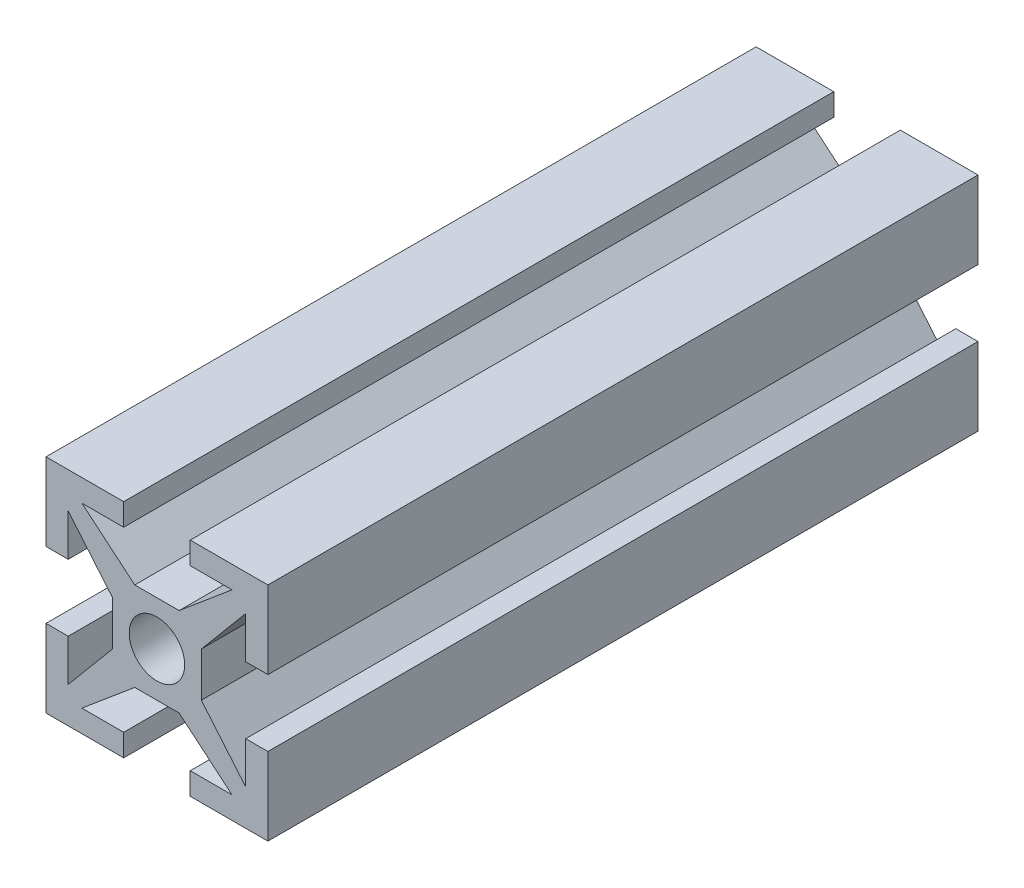
SolidWorks part; units mm, degrees
ref_plane "Front Plane" through (0, 0, 0) normal (0, 0, 1) x (1, 0, 0)
ref_plane "Top Plane" through (0, 0, 0) normal (0, 1, 0) x (1, 0, 0)
ref_plane "Right Plane" through (0, 0, 0) normal (1, 0, 0) x (0, 0, -1)
sketch "Esquisse2" plane through (0, 0, 0) normal (0, 0, 1) x (1, 0, 0)
  line L0 (-1, -2) -> (1, -2)
  line L1 (1, -2) -> (3.3835, -4)
  line L2 (3.3835, -4) -> (1.5, -4)
  line L3 (1.5, -4) -> (1.5, -5)
  line L4 (1.5, -5) -> (5, -5)
  line L5 (-1, -2) -> (-3.3835, -4)
  line L6 (-3.3835, -4) -> (-1.5, -4)
  line L7 (-1.5, -4) -> (-1.5, -5)
  line L8 (-1.5, -5) -> (-5, -5)
  line L9 (-5, -5) -> (-5, -1.5)
  line L10 (-5, -1.5) -> (-4, -1.5)
  line L11 (-4, -1.5) -> (-4, -3.3835)
  line L12 (-4, -3.3835) -> (-2, -1)
  line L13 (-2, -1) -> (-2, 1)
  line L14 (-2, 1) -> (-4, 3.3835)
  line L15 (-4, 3.3835) -> (-4, 1.5)
  line L16 (-4, 1.5) -> (-5, 1.5)
  line L17 (-5, 1.5) -> (-5, 5)
  line L18 (-5, 5) -> (-1.5, 5)
  line L19 (-1.5, 5) -> (-1.5, 4)
  line L20 (-1.5, 4) -> (-3.3835, 4)
  line L21 (-3.3835, 4) -> (-1, 2)
  line L22 (-1, 2) -> (1, 2)
  line L23 (1, 2) -> (3.3835, 4)
  line L24 (3.3835, 4) -> (1.5, 4)
  line L25 (1.5, 4) -> (1.5, 5)
  line L26 (1.5, 5) -> (5, 5)
  line L27 (5, 5) -> (5, 1.5)
  line L28 (5, 1.5) -> (4, 1.5)
  line L29 (4, 1.5) -> (4, 3.3835)
  line L30 (4, 3.3835) -> (2, 1)
  line L31 (2, -1) -> (2, 1)
  line L32 (2, -1) -> (4, -3.3835)
  line L33 (4, -3.3835) -> (4, -1.5)
  line L34 (4, -1.5) -> (5, -1.5)
  line L35 (5, -1.5) -> (5, -5)
  circle A0 centre (0, 0) radius 1.25
  point P4 (0, -2)
  point P34 (0, 2)
  point P40 (2, 0)
  dimension "D4" = 2.5
  dimension "D1" = 2
  dimension "D2" = 3.5
  dimension "D3" = 1
  dimension "D5" = 10
  dimension "D6" = 10
  dimension "D7" = 140
  dimension "D8" = 4
  dimension "D9" = 4
  dimension "D10" = 3.5
  dimension "D11" = 3
extrude "Main Extrusion" add sketch "Esquisse2" along normal blind 32
